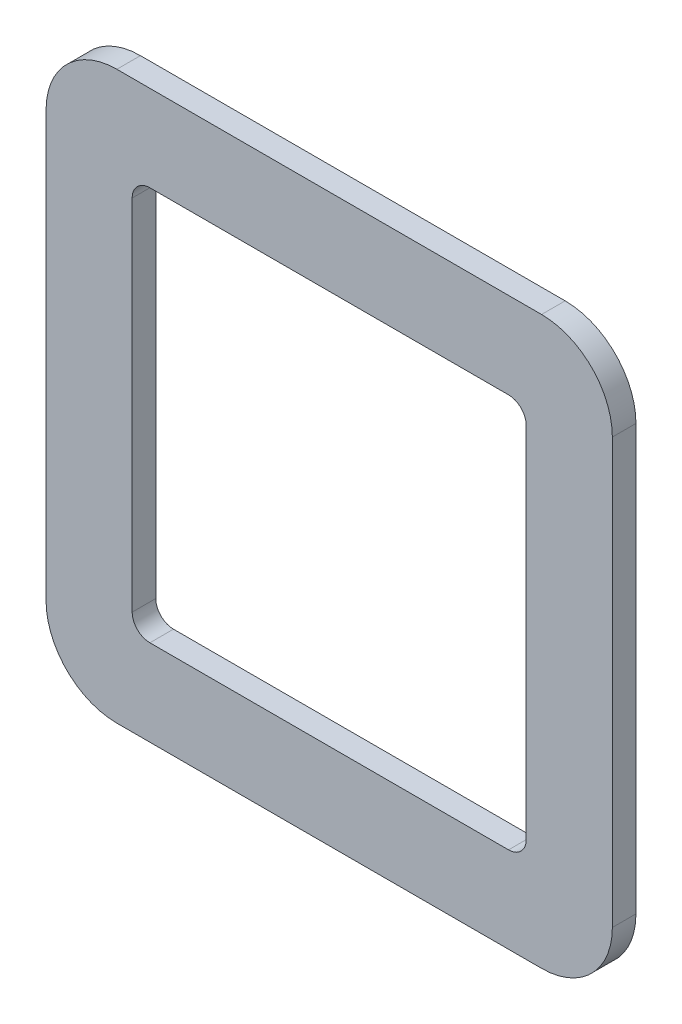
SolidWorks part; units mm, degrees
ref_plane "front" through (0, 0, 0) normal (0, 0, 1) x (1, 0, 0)
ref_plane "top" through (0, 0, 0) normal (0, 1, 0) x (1, 0, 0)
ref_plane "right" through (0, 0, 0) normal (1, 0, 0) x (0, 0, -1)
ref_axis "Axis1" through (0, 0, -69.7337) along (0, 0, 1)
sketch "Sketch1" plane through (0, 0, 0) normal (0, 0, 1) x (1, 0, 0)
  line L0 (-1.9558, 1.9558) -> (1.9558, 1.9558)
  line L1 (1.9558, 1.9558) -> (1.9558, -1.9558)
  line L2 (1.9558, -1.9558) -> (-1.9558, -1.9558)
  line L3 (-1.9558, -1.9558) -> (-1.9558, 1.9558)
  line L4 (-1.9558, 0) -> (-22.3549, 0) construction
  line L5 (-22.3549, 0) -> (0, 3.9418)
  line L6 (-22.3549, 0) -> (0, 1.9558)
  line L7 (-22.3549, 0) -> (0, 3.0424)
  dimension "D1" = 10
  dimension "D2" = 5
  dimension "D3" = 22.3549
  dimension "D4" = 22.6998
  dimension "D5" = 2.25
sketch "Sketch2" plane through (0, 0, 0) normal (0, 0, 1) x (1, 0, 0)
  line L1 (-0.1524, 3.7084) -> (-0.1524, 3.048)
  line L2 (0.6096, 4.318) -> (3.6576, 4.318)
  line L4 (2.0066, 0.762) -> (3.9116, 0.762)
  line L5 (3.9116, 0.762) -> (3.9116, 4.064)
  line L6 (0.4318, 3.9116) -> (0.3556, 3.9116)
  line L7 (0, 4.1205) -> (0, 6.0044) construction
  line L8 (0.1524, 3.7084) -> (0.1524, 3.048)
  line L9 (-0.3556, 3.9116) -> (-0.889, 3.9116)
  line L10 (0.5588, 4.2672) -> (0.5588, 4.0386)
  line L14 (0.0508, 2.9464) -> (-0.0508, 2.9464)
  line L15 (-0.889, 3.9116) -> (-0.889, 2.0066)
  line L16 (-0.889, 2.0066) -> (1.905, 2.0066)
  line L24 (-1.9558, 1.9558) -> (1.9558, 1.9558) construction
  line L25 (1.9558, 1.9558) -> (1.9558, -1.9558) construction
  line L26 (2.0066, 1.905) -> (2.0066, 0.762)
  arc A0 (0.1524, 3.048) -> (0.0508, 2.9464) centre (0.0508, 3.048) cw
  arc A1 (-0.1524, 3.048) -> (-0.0508, 2.9464) centre (-0.0508, 3.048) ccw
  arc A2 (3.6576, 4.318) -> (3.9116, 4.064) centre (3.6576, 4.064) cw
  arc A3 (0.3556, 3.9116) -> (0.1524, 3.7084) centre (0.3556, 3.7084) ccw
  arc A4 (-0.3556, 3.9116) -> (-0.1524, 3.7084) centre (-0.3556, 3.7084) cw
  circle A5 centre (0, 0) radius 1.6256 construction
  arc A6 (1.905, 2.0066) -> (2.0066, 1.905) centre (1.905, 1.905) cw
  arc A9 (0.5588, 4.0386) -> (0.4318, 3.9116) centre (0.4318, 4.0386) cw
  arc A10 (0.6096, 4.318) -> (0.5588, 4.2672) centre (0.6096, 4.2672) ccw
  point P29 (0.1524, 3.9116)
  dimension "D3" = 0.254
  dimension "D14" = 0.0508
  dimension "D6" = 0.1016
  dimension "D2" = 3.9116
  dimension "D7" = 0.1016
  dimension "D11" = 0.2032
  dimension "D8" = 3.2512
  dimension "D19" = 0.0302
  dimension "D20" = 0.127
  dimension "D21" = 0.0508
  dimension "D4" = 2.9464
  dimension "D5" = 0.3048
  dimension "D12" = 0.0508
  dimension "D13" = 0.762
  dimension "D15" = 3.9116
  dimension "D22" = 0.4064
  dimension "D23" = 0.5588
  dimension "D29" = 0.889
sketch "Sketch3" plane through (0, 0, 0) normal (0, 0, 1) x (1, 0, 0)
  line L0 (4.2418, 0.762) -> (6.096, 0.762)
  line L1 (6.096, 0.762) -> (6.096, 4.572)
  line L2 (4.572, 6.096) -> (-0.889, 6.096)
  line L3 (-0.889, 6.096) -> (-0.889, 4.2418)
  line L4 (-0.889, 4.2418) -> (3.8608, 4.2418)
  line L7 (4.2418, 3.8608) -> (4.2418, 0.762)
  line L8 (3.9116, 0.762) -> (3.9116, 4.064) construction
  line L10 (-0.3556, 3.9116) -> (-0.889, 3.9116) construction
  arc A0 (6.096, 4.572) -> (4.572, 6.096) centre (4.572, 4.572) ccw
  arc A1 (3.8608, 4.2418) -> (4.2418, 3.8608) centre (3.8608, 3.8608) cw
  dimension "D2" = 0.381
  dimension "D3" = 1.524
  dimension "D1" = 0.3302
  dimension "D4" = 6.096
  dimension "D5" = 6.096
  dimension "D8" = 0.3302
extrude "Boss-Extrude1" add sketch "Sketch3" along normal mid plane 0.508
pattern_circular "CirPattern2" count 4 over 360 about axis through (0, 0, -69.7337) along (0, 0, 1) of "Boss-Extrude1"
pattern_linear "LPattern1" [suppressed] count 7 spacing 13.7668 count 7 spacing 13.7668 of bodies 109
